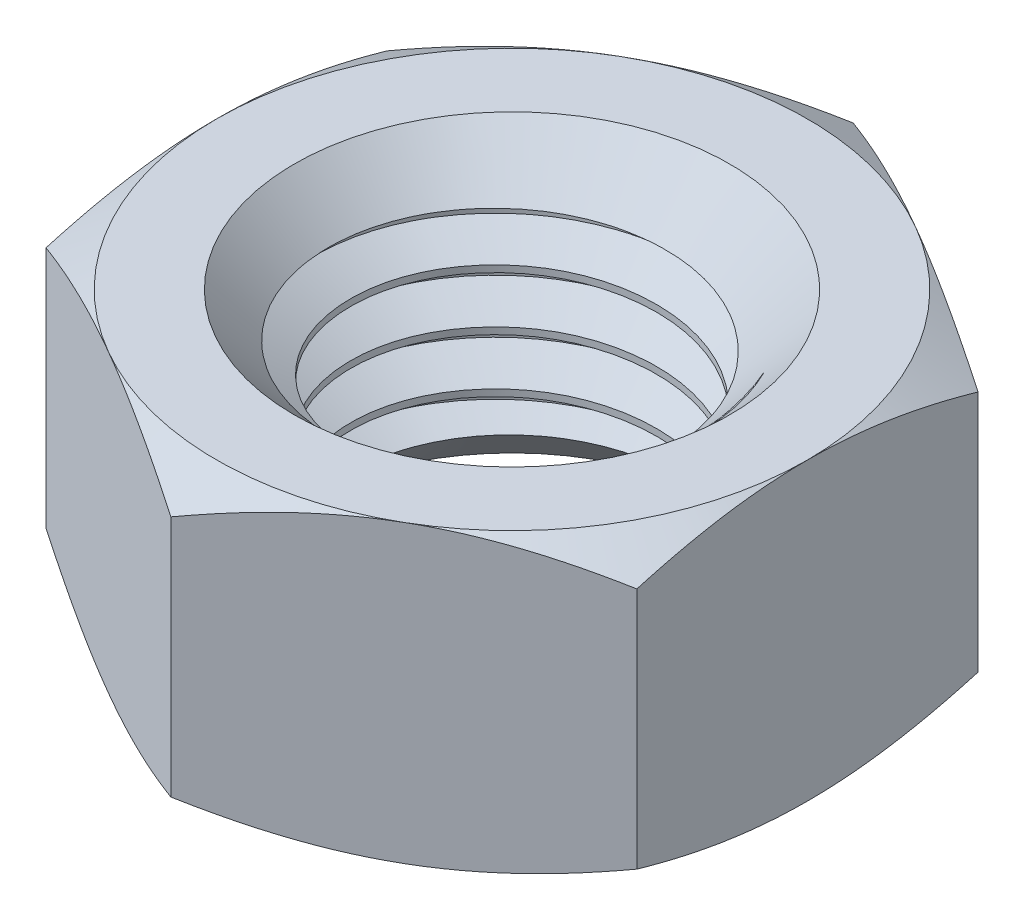
SolidWorks part; units mm, degrees
ref_plane "Front Plane" through (0, 0, 0) normal (0, 0, 1) x (1, 0, 0)
ref_plane "Top Plane" through (0, 0, 0) normal (0, 1, 0) x (1, 0, 0)
ref_plane "Right Plane" through (0, 0, 0) normal (1, 0, 0) x (0, 0, -1)
sketch "Sketch1" plane through (0, 0, 0) normal (0, 1, 0) x (1, 0, 0)
  line L1 (5.5, 3.1754) -> (0, 6.3509) construction
  line L2 (0, 6.3509) -> (-5.5, 3.1754) construction
  line L3 (-5.5, 3.1754) -> (-5.5, -3.1754) construction
  line L4 (-5.5, -3.1754) -> (0, -6.3509) construction
  line L5 (0, -6.3509) -> (5.5, -3.1754) construction
  line L6 (5.5, -3.1754) -> (5.5, 3.1754) construction
  line L7 (0, -2.5) -> (0, -3.5) construction
  circle A0 centre (0, 0) radius 5.5 construction
  circle A1 centre (0, 0) radius 3.5 construction
  point P10 (0, -3.5)
  dimension "Thread Size" = 7
  dimension "Width" = 11
  dimension "Thread Pitch" = 1
sketch "Sketch9" plane through (0, 0, 0) normal (0, 0, 1) x (1, 0, 0)
  line L0 (0, 2.75) -> (0, -2.75) construction
  dimension "Height" = 5.5
sketch "Sketch2" plane through (0, 0, 0) normal (0, 1, 0) x (1, 0, 0)
  line L0 (-5.5, -3.1754) -> (0, -6.3509) construction
  line L1 (0, -6.3509) -> (5.5, -3.1754) construction
  line L2 (5.5, -3.1754) -> (5.5, 3.1754) construction
  line L3 (5.5, 3.1754) -> (0, 6.3509) construction
  line L4 (0, 6.3509) -> (-5.5, 3.1754) construction
  line L5 (-5.5, 3.1754) -> (-5.5, -3.1754) construction
  line L6 (-5.5, -3.1754) -> (0, -6.3509)
  line L7 (0, -6.3509) -> (5.5, -3.1754)
  line L8 (5.5, -3.1754) -> (5.5, 3.1754)
  line L9 (5.5, 3.1754) -> (0, 6.3509)
  line L10 (0, 6.3509) -> (-5.5, 3.1754)
  line L11 (-5.5, 3.1754) -> (-5.5, -3.1754)
  circle A0 centre (0, 0) radius 3.5 construction
  circle A1 centre (0, 0) radius 3.5
extrude "Boss-Extrude1" add sketch "Sketch2" along normal mid plane 5.5
sketch "Sketch3" plane through (0, 2.75, 0) normal (0, 1, 0) x (1, 0, 0)
  circle A2 centre (0, 0) radius 5.5 construction
  circle A3 centre (0, 0) radius 5.5
extrude "Cut-Extrude1" cut sketch "Sketch3" against normal through all draft 60 flip side to cut
mirror "Mirror1" about plane through (0, 0, 0) normal (0, 1, 0) of "Cut-Extrude1"
chamfer "Chamfer1" distance 0.55 angle 45 2 edges at (0, -2.75, 3.5) (0, 2.75, 3.5)
sketch "Sketch4" plane through (0, 2.75, 0) normal (0, 1, 0) x (1, 0, 0)
  circle A2 centre (0, 0) radius 3.5 construction
  circle A3 centre (0, 0) radius 3.5
curve "Helix/Spiral1" pitch 1 height 6.5 radius 3.5 centre (0, 2.75, 0) axis (0, -1, 0) start towards (0, 0, 1)
sketch "Sketch5" plane through (0, 0, 0) normal (0, 0, 1) x (1, 0, 0)
  line L4 (-3.6083, 2.6875) -> (-2.7422, 3.1875) construction
  line L5 (-2.7422, 3.1875) -> (-3.6083, 3.6875) construction
  line L6 (-3.6083, 3.6875) -> (-3.6083, 2.6875) construction
  line L7 (-3.5, 2.75) -> (-3.5, 3.625) construction
  line L8 (-3.6083, 3.1875) -> (-3.5, 3.1875) construction
  line L9 (-3.5, 3.1875) -> (-2.8505, 3.1875) construction
  line L10 (-2.8505, 3.1875) -> (-2.7422, 3.1875) construction
  line L11 (-2.8505, 3.125) -> (-2.8505, 3.25)
  line L12 (-3.5541, 2.7188) -> (-3.5541, 3.6562)
  line L13 (-2.8505, 3.25) -> (-3.5541, 3.6562)
  line L14 (-2.8505, 3.125) -> (-3.5541, 2.7188)
  point P13 (-3.5541, 3.1875)
  dimension "D2" = 0.125
sweep "Sweep1" add profiles "Sketch5" path "Helix/Spiral1"
sketch "Sketch6" plane through (0, 2.75, 0) normal (0, 1, 0) x (1, 0, 0)
  circle A0 centre (0, 0) radius 4.05 construction
  circle A3 centre (0, 0) radius 4.05
extrude "Cut-Extrude2" cut sketch "Sketch6" along normal through all and the other way blind 10 draft 45
sketch "Sketch10" plane through (0, -2.75, 0) normal (0, -1, 0) x (1, 0, 0)
  circle A1 centre (0, 0) radius 4.05
  circle A2 centre (0, 0) radius 4.05
  dimension "D1" = 0
extrude "Cut-Extrude3" cut sketch "Sketch10" against normal through all draft 45 and the other way through all
equation "\"D1@Boss-Extrude1\" = \"Height@Sketch9\""
equation "\"D3@Helix/Spiral1\"= \"Height@Sketch9\" + \"Thread Pitch@Sketch1\""
equation "\"D4@Helix/Spiral1\" = \"Thread Pitch@Sketch1\""
equation "\"D2@Sketch5\"=\"D1@Sketch5\"/8"
equation "\"D1@Sketch5\"=\"Thread Pitch@Sketch1\""
equation "\"D1@Chamfer1\"=\"Thread Pitch@Sketch1\"*0.55"
